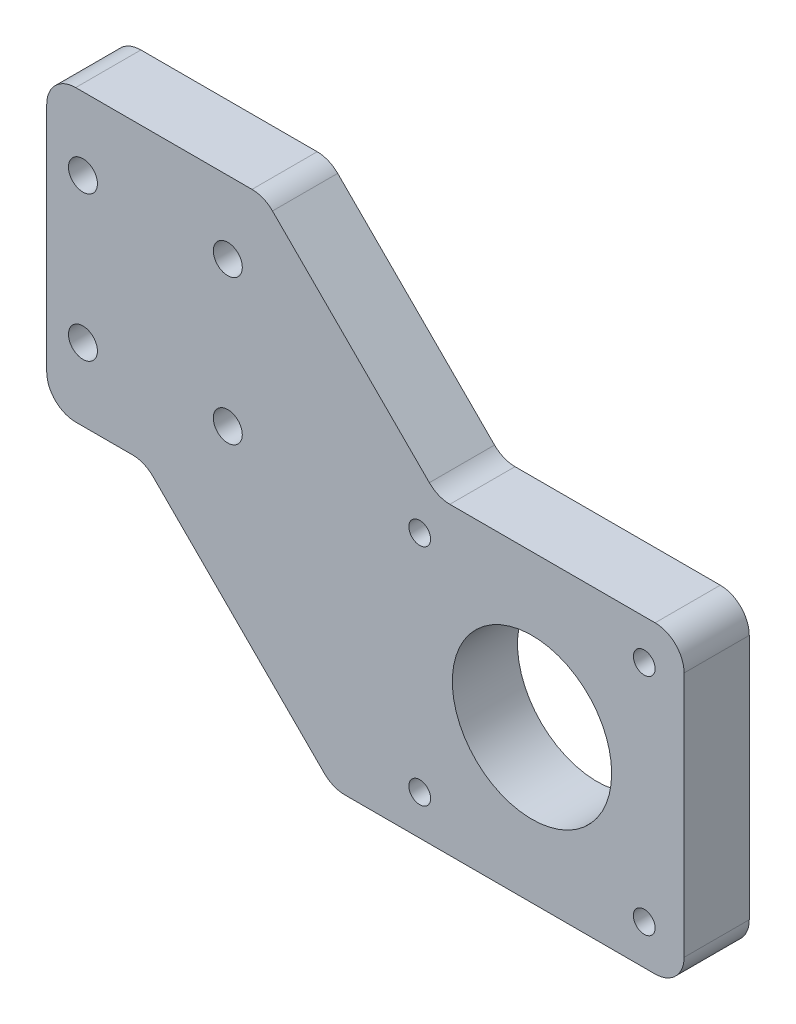
SolidWorks part; units mm, degrees
ref_plane "Front" through (0, 0, 0) normal (0, 0, 1) x (1, 0, 0)
ref_plane "Top" through (0, 0, 0) normal (0, 1, 0) x (1, 0, 0)
ref_plane "Right" through (0, 0, 0) normal (1, 0, 0) x (0, 0, -1)
sketch "Esquisse1" plane through (0, 0, 0) normal (0, 0, 1) x (1, 0, 0)
  line L1 (0, 0) -> (88, 0)
  line L2 (0, 0) -> (0, 96)
  line L3 (0, 96) -> (88, 96)
  line L4 (88, 0) -> (88, 96)
  dimension "D1" = 96
  dimension "D2" = 88
extrude "Boss.-Extru.1" add sketch "Esquisse1" along normal blind 9
sketch "Esquisse2" plane through (0, 0, 9) normal (0, 0, 1) x (1, 0, 0)
  line L0 (0, 48) -> (5, 48) construction
  line L1 (0, 96) -> (0, 0) construction
  line L2 (5, 48) -> (5, 58) construction
  line L3 (5, 48) -> (15, 48) construction
  line L4 (15, 48) -> (15, 25.2533) construction
  line L5 (25, 48) -> (25, 58) construction
  circle A0 centre (5, 58) radius 2
  circle A1 centre (5, 38) radius 2
  circle A2 centre (25, 38) radius 2
  circle A3 centre (25, 58) radius 2
  dimension "D3" = 4
  dimension "D1" = 20
  dimension "D2" = 5
  dimension "D4" = 20
extrude "Enlèv. mat.-Extru.1" cut sketch "Esquisse2" against normal through all
sketch "Esquisse3" plane through (0, 0, 9) normal (0, 0, 1) x (1, 0, 0)
  line L0 (67, 96) -> (67, 0) construction
  line L1 (88, 96) -> (0, 96) construction
  line L2 (0, 0) -> (88, 0) construction
  line L3 (67, 23) -> (81.7886, 23) construction
  line L4 (25, 38) -> (25, 58) construction
  line L5 (25, 48) -> (33.6252, 48) construction
  circle A0 centre (82.5, 38.5) radius 1.5
  circle A1 centre (82.5, 7.5) radius 1.5
  circle A2 centre (51.5, 7.5) radius 1.5
  circle A3 centre (51.5, 38.5) radius 1.5
  circle A4 centre (25, 58) radius 2 construction
  circle A5 centre (67, 23) radius 11
  dimension "D1" = 3
  dimension "D2" = 31
  dimension "D3" = 31
  dimension "D5" = 22
  dimension "D4" = 42
  dimension "D6" = 25
extrude "Enlèv. mat.-Extru.2" cut sketch "Esquisse3" against normal through all
sketch "Esquisse4" plane through (0, 0, 9) normal (0, 0, 1) x (1, 0, 0)
  line L0 (88, 0) -> (88, 96) construction
  line L1 (0, 96) -> (88, 96)
  line L2 (0, 96) -> (0, 68)
  line L3 (0, 68) -> (88, 68)
  line L4 (88, 96) -> (88, 68)
  circle A0 centre (5, 58) radius 2 construction
  dimension "D1" = 10
extrude "Enlèv. mat.-Extru.3" cut sketch "Esquisse4" against normal through all
sketch "Esquisse5" plane through (0, 0, 9) normal (0, 0, 1) x (1, 0, 0)
  line L0 (30, 68) -> (54, 44)
  line L1 (0, 68) -> (88, 68) construction
  line L2 (54, 44) -> (88, 44)
  line L3 (88, 0) -> (88, 68) construction
  line L5 (30, 68) -> (88, 68)
  line L6 (88, 68) -> (88, 44)
  circle A0 centre (25, 58) radius 2 construction
  circle A1 centre (82.5, 38.5) radius 1.5 construction
  dimension "D1" = 5.5
  dimension "D2" = 135
  dimension "D3" = 5
extrude "Enlèv. mat.-Extru.4" cut sketch "Esquisse5" against normal up to vertex (9 mm away) up to point (88, 68, 0)
sketch "Esquisse6" plane through (0, 0, 9) normal (0, 0, 1) x (1, 0, 0)
  line L1 (0, 0) -> (41.5, 0)
  line L2 (0, 0) -> (0, 28)
  line L3 (0, 28) -> (41.5, 28)
  line L4 (41.5, 0) -> (41.5, 28)
  circle A0 centre (5, 38) radius 2 construction
  circle A1 centre (51.5, 7.5) radius 1.5 construction
  dimension "D1" = 10
  dimension "D2" = 10
extrude "Enlèv. mat.-Extru.5" cut sketch "Esquisse6" against normal through all
sketch "Esquisse7" plane through (0, 0, 9) normal (0, 0, 1) x (1, 0, 0)
  line L0 (88, 0) -> (88, 44) construction
  line L1 (41.5, 0) -> (88, 0)
  line L2 (41.5, 0) -> (41.5, 2)
  line L3 (41.5, 2) -> (88, 2)
  line L4 (88, 0) -> (88, 2)
  circle A0 centre (82.5, 7.5) radius 1.5 construction
  dimension "D1" = 5.5
extrude "Enlèv. mat.-Extru.6" cut sketch "Esquisse7" against normal through all
chamfer "Chanfrein1" distance 28 angle 45 1 edges at (41.5, 28, 4.5)
fillet "Congé1" radius 4 8 edges at (88, 44, 4.5) (54, 44, 4.5) (30, 68, 4.5) (0, 68, 4.5) (13.5, 28, 4.5) (0, 28, 4.5) (88, 2, 4.5) (39.5, 2, 4.5)
